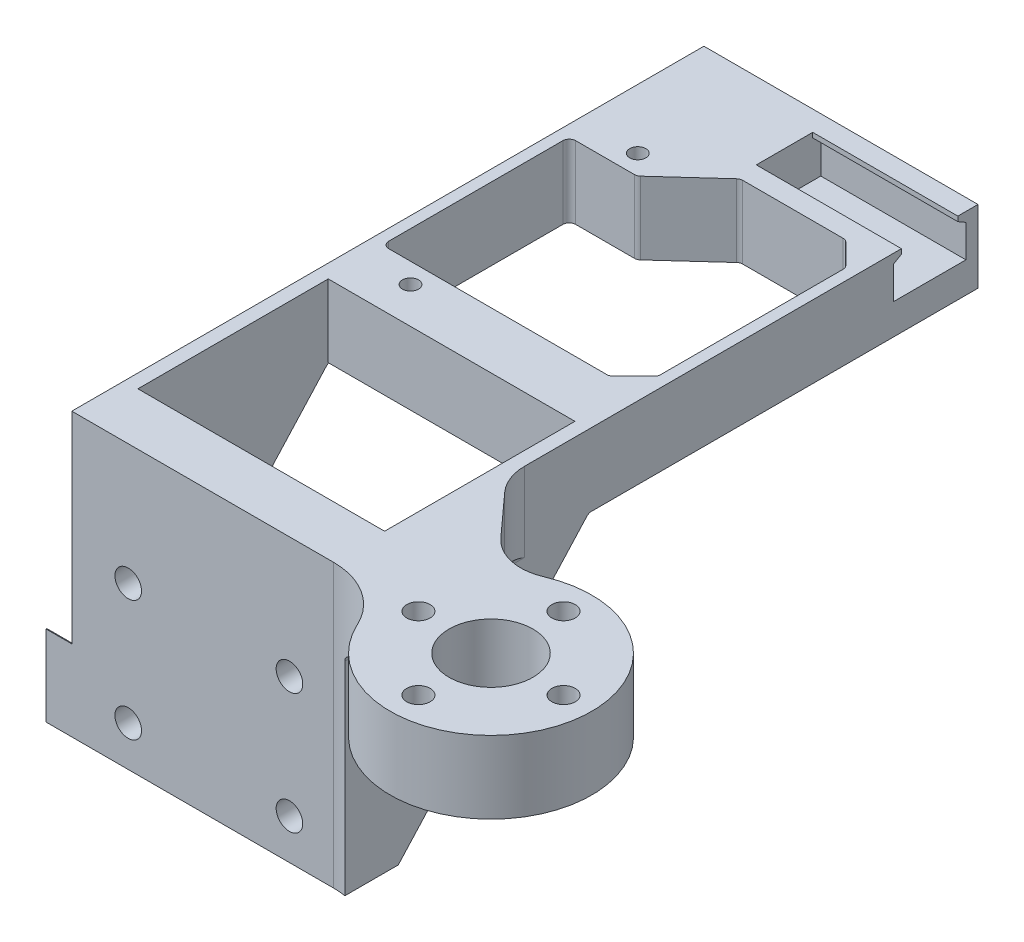
SolidWorks part; units mm, degrees
ref_plane "Front Plane" through (0, 0, 0) normal (0, 0, 1) x (1, 0, 0)
ref_plane "Top Plane" through (0, 0, 0) normal (0, 1, 0) x (1, 0, 0)
ref_plane "Right Plane" through (0, 0, 0) normal (1, 0, 0) x (0, 0, -1)
sketch "Sketch1" plane through (0, 0, 0) normal (0, 1, 0) x (1, 0, 0)
  line L0 (0, 0) -> (0, 59.6401) construction
  line L1 (-20, -19.2885) -> (-21.4, -19.2885)
  line L2 (20, 17.7115) -> (21.4, 17.7115)
  line L3 (20, 17.7115) -> (20, 69.9115)
  line L4 (20, 69.9115) -> (21.4, 69.9115)
  line L5 (21.4, 17.7115) -> (21.4, 69.9115)
  line L6 (20, 17.7115) -> (21.4, 17.7115)
  line L7 (20, 17.7115) -> (20, -19.2885)
  line L8 (20, -19.2885) -> (21.4, -19.2885)
  line L9 (21.4, 17.7115) -> (21.4, -19.2885)
  line L10 (-21.4, 17.7115) -> (-21.4, -19.2885)
  line L11 (-20, 17.7115) -> (-21.4, 17.7115)
  line L12 (-20, 17.7115) -> (-20, -19.2885)
  line L13 (-20, 69.9115) -> (-21.4, 69.9115)
  line L14 (-21.4, 17.7115) -> (-21.4, 69.9115)
  line L15 (-20, 17.7115) -> (-21.4, 17.7115)
  line L16 (-20, 17.7115) -> (-20, 69.9115)
  dimension "18" = 20
  dimension "D2" = 1.4
  dimension "D3" = 37
  dimension "D4" = 52.2
extrude "Boss-Extrude1" add sketch "Sketch1" against normal blind 9 from offset 1 contours L12 L11 L10 L1 | L11 L16 L13 L14 | L3 L2 L5 L4 offset against normal yes
sketch "Sketch4" plane through (0, -10, 0) normal (0, -1, 0) x (1, 0, 0)
  line L0 (-21.4, -69.9115) -> (-21.4, 19.2885) construction
  line L1 (12, -69.9115) -> (-21.4, -69.9115)
  line L2 (12, -69.9115) -> (12, -57.9115)
  line L3 (12, -57.9115) -> (-21.4, -57.9115)
  line L4 (-21.4, -69.9115) -> (-21.4, -57.9115)
  line L10 (-20, -69.9115) -> (-20, 19.2885) construction
  line L13 (-20, -69.9115) -> (-21.4, -69.9115) construction
  dimension "D1" = 12
  dimension "D2" = 32
extrude "Boss-Extrude3" add sketch "Sketch4" against normal up to surface (9 mm away) up to face at (-20.7, -1, -25.3115)
sketch "Sketch3" plane through (0, -10, 0) normal (0, -1, 0) x (1, 0, 0)
  line L0 (-21.4, -69.9115) -> (-21.4, 19.2885) construction
  line L1 (-21.4, -58.8115) -> (-7.4, -58.8115)
  line L2 (-21.4, -58.8115) -> (-21.4, -51.8115)
  line L3 (-21.4, -51.8115) -> (-7.4, -51.8115)
  line L4 (-7.4, -58.8115) -> (-7.4, -51.8115)
  line L6 (0, 0) -> (0, -31.4212) construction
  line L13 (12, -69.9115) -> (-21.4, -69.9115) construction
  line L14 (-21.4, -40.2115) -> (-3.8096, -40.2115) construction
  line L15 (-21.4, -28.6115) -> (-7.4, -28.6115)
  line L16 (-7.4, -21.6115) -> (-7.4, -28.6115)
  line L17 (-21.4, -21.6115) -> (-7.4, -21.6115)
  line L18 (-21.4, -21.6115) -> (-21.4, -28.6115)
  line L19 (-20, -57.9115) -> (-20, 19.2885) construction
  circle A0 centre (-14, -54.3115) radius 1
  circle A2 centre (-14, -26.1115) radius 1
  dimension "D4" = 2.5
  dimension "D5" = 2
  dimension "D1" = 14.1
  dimension "D2" = 15.6
  dimension "D3" = 7
  dimension "D6" = 6
  dimension "D7" = 14
extrude "Servo Holder" add sketch "Sketch3" along normal blind 1 and the other way offset from surface (9 mm away) 1 other way up to plane "Top Plane"
sketch "Sketch37" plane through (0, -1, 0) normal (0, 1, 0) x (1, 0, 0)
  line L0 (-7.4, 21.6115) -> (-20, 21.6115) construction
  line L1 (12.6, 21.6115) -> (-7.4, 21.6115)
  line L2 (12.6, 21.6115) -> (12.6, 28.6115)
  line L3 (12.6, 28.6115) -> (-7.4, 28.6115)
  line L4 (-7.4, 21.6115) -> (-7.4, 28.6115)
  line L5 (-21.4, 69.9115) -> (-21.4, -19.2885) construction
  dimension "D1" = 34
extrude "Boss-Extrude19" add sketch "Sketch37" against normal up to surface (10 mm away) up to face at (-14.4, -11, -25.1115)
sketch "Sketch29" plane through (0, 0, -69.9115) normal (0, 0, -1) x (-1, 0, 0)
  line L1 (21.4, -10) -> (-12.7099, -10)
  line L2 (21.4, -10) -> (21.4, -16.1774)
  line L3 (21.4, -16.1774) -> (-12.7099, -16.1774)
  line L4 (-12.7099, -10) -> (-12.7099, -16.1774)
extrude "Cut-Extrude10" cut sketch "Sketch29" against normal through all both and the other way through all
sketch "Sketch30" plane through (0, 0, 0) normal (0, 0, 1) x (1, 0, 0)
  line L0 (-4.4, -1) -> (-4.4, -36) construction
  line L1 (12.6, -1) -> (-21.4, -1)
  line L2 (12.6, -1) -> (12.6, -36)
  line L3 (12.6, -36) -> (-21.4, -36)
  line L4 (-21.4, -1) -> (-21.4, -36)
  line L7 (-21.4, -1) -> (12.6, -1) construction
  line L9 (12.6, -1) -> (-20, -1) construction
  line L11 (-21.4, -10) -> (-21.4, -1) construction
  circle A0 centre (5.6, -31) radius 1.65
  circle A1 centre (5.6, -16) radius 1.65
  circle A2 centre (-14.4, -31) radius 1.65
  circle A3 centre (-14.4, -16) radius 1.65
  dimension "D2" = 10
  dimension "D4" = 15
  dimension "D7" = 3.3
  dimension "D8" = 3.3
  dimension "D1" = 17
  dimension "D3" = 35
  dimension "D5" = 15
  dimension "D6" = 10
extrude "Carriage Interface" add sketch "Sketch30" along normal blind 6.5 from offset 2 separate body
sketch "Sketch41" plane through (-20, 0, 0) normal (1, 0, 0) x (0, 0, -1)
  line L0 (21.6115, -1) -> (-19.2885, -1) construction
  line L1 (-2, -1) -> (-19.2885, -1)
  line L2 (-2, -1) -> (-2, -10)
  line L3 (-2, -10) -> (-19.2885, -10)
  line L4 (-19.2885, -1) -> (-19.2885, -10)
  line L5 (-2, -1) -> (-2, -36) construction
extrude "Cut-Extrude14" cut sketch "Sketch41" against normal blind 15
sketch "Sketch32" plane through (0, -36, 0) normal (0, -1, 0) x (1, 0, 0)
  line L0 (-21.4, 8.5) -> (12.6, 8.5) construction
  line L1 (30.6, 8.5) -> (18.1, 8.5) construction
  line L2 (30.6, 8.5) -> (12.6, 8.5) construction
  line L4 (-21.4, 8.5) -> (12.6, 8.5) construction
  circle A0 centre (30.6, 8.5) radius 5.2
  circle A1 centre (30.6, 8.5) radius 12.5
  circle A2 centre (21.6, 8.5) radius 1.45
  circle A3 centre (30.6, 17.5) radius 1.45
  circle A4 centre (39.6, 8.5) radius 1.45
  circle A5 centre (30.6, -0.5) radius 1.45
  point P4 (-4.4, 8.5)
  point P18 (30.6, 8.5)
  line M1 (-21.4, 2) -> (12.6, 2)
  line M2 (12.6, 2) -> (12.6, 8.5)
  line M3 (12.6, 8.5) -> (-21.4, 8.5)
  dimension "D1" = 9
  dimension "D2" = 25
  dimension "D4" = 10.4
  dimension "D5" = 35
  dimension "D3" = 4
extrude "Trap Nut Interface" add sketch "Sketch32" along normal blind 9 from surface at -35 contours A1 A5 A4 A3 A2 A0 M1 M3 M2 starting at face at (-3.7, -1, 5.25)
sketch "Sketch34" plane through (-21.4, 0, 0) normal (-1, 0, 0) x (0, 0, 1)
  line L1 (-21.6115, -1) -> (-21.6115, -10)
  line L5 (-69.9115, -1) -> (2, -1) construction
  line L6 (-69.9115, -10) -> (2, -10) construction
  line L7 (-21.6115, -10) -> (2, -36)
  line L8 (-21.6115, -10) -> (-21.6115, -1) construction
  line L9 (2, -36) -> (8.5, -36)
  line L10 (8.5, -36) -> (8.5, -1)
  line L11 (8.5, -1) -> (-21.6115, -1)
extrude "Boss-Extrude16" add sketch "Sketch34" against normal blind 1.7
sketch "Sketch35" plane through (12.6, 0, 0) normal (1, 0, 0) x (0, 0, -1)
  line L0 (-2, -1) -> (21.6115, -1)
  line L1 (21.6115, -1) -> (21.6115, -10)
  line L3 (-8.5, -9.8) -> (-8.5, -1)
  line L4 (-8.5, -1) -> (-2, -1)
  line L5 (21.6115, -10) -> (21.6115, -1) construction
  line L6 (28.6115, -10) -> (21.6115, -10) construction
  line L8 (-8.5, -36) -> (-8.5, -1) construction
  line L9 (21.6115, -1) -> (28.6115, -1) construction
  line L10 (21.6115, -10) -> (-2, -36)
  line L11 (-2, -36) -> (-8.5, -36)
  line L12 (-8.5, -36) -> (-8.5, -9.8)
extrude "Boss-Extrude17" add sketch "Sketch35" against normal blind 1.7
sketch "Sketch36" plane through (0, -10, 0) normal (0, -1, 0) x (1, 0, 0)
  line L0 (12.6, -11.3656) -> (22.2068, -0.7631)
  line L1 (12.6, 8.5) -> (19.7685, 8.5)
  line L2 (22.2068, -0.7631) -> (12.6, -0.1224)
  line L3 (12.6, -0.1224) -> (12.6, -11.3656)
  line L4 (30.6, 8.5) -> (12.6, -11.3656) construction
  line L5 (12.6, 8.5) -> (12.6, 2) construction
  line L6 (19.7685, 8.5) -> (22.2068, -0.7631)
  line L7 (12.6, 8.5) -> (12.6, -0.1224)
  circle A1 centre (30.6, 8.5) radius 12.5 construction
  point P8 (20.15, 8.5)
  point P13 (19.7685, 8.5)
  point P15 (20.15, 8.5)
extrude "Boss-Extrude18" add sketch "Sketch36" against normal up to surface (9 mm away) contours L1 L7 L2 L6 | L2 L3 L0
fillet "Fillet9" [suppressed] radius 1
sketch "Sketch39" plane through (0, -1, 0) normal (0, 1, 0) x (1, 0, 0)
  line L0 (-21.4, 69.9115) -> (12, 69.9115) construction
  line L1 (12.6, 28.6115) -> (11.2, 28.6115)
  line L2 (12.6, 28.6115) -> (12.6, 69.9115)
  line L3 (12.6, 69.9115) -> (11.2, 69.9115)
  line L4 (11.2, 28.6115) -> (11.2, 69.9115)
  line L5 (-20, 28.6115) -> (12.6, 28.6115) construction
  line L6 (12.6, 11.3656) -> (12.6, 28.6115) construction
  point P7 (12.6, 49.2615)
  dimension "D1" = 1.4
extrude "Boss-Extrude20" add sketch "Sketch39" against normal up to surface (9 mm away) up to face at (-4.7667, -10, -41.9115)
sketch "Sketch40" plane through (12.6, 0, 0) normal (1, 0, 0) x (0, 0, -1)
  line L1 (60.4115, -1) -> (67.4115, -1)
  line L6 (60.4115, -2.2) -> (59.4115, -2.2)
  line L7 (59.4115, -2.2) -> (59.4115, -6.2)
  line L8 (59.4115, -6.2) -> (68.4115, -6.2)
  line L9 (63.9115, -6.2) -> (63.9115, -1)
  line L11 (68.4115, -2.2) -> (68.4115, -6.2)
  line L12 (67.4115, -2.2) -> (68.4115, -2.2)
  line L13 (67.4115, -1) -> (67.4115, -2.2)
  line L14 (69.9115, -10) -> (69.9115, -1) construction
  line L15 (60.4115, -2.2) -> (60.4115, -1)
  line L16 (11.3656, -1) -> (69.9115, -1) construction
  point P9 (59.4115, -4.2)
  dimension "D1" = 6
  dimension "D2" = 3.5
  dimension "D3" = 4.5
  dimension "D4" = 4
  dimension "D5" = 1.2
  dimension "D6" = 3.5
  dimension "D7" = 1
extrude "Brush" cut sketch "Sketch40" against normal blind 18
chamfer "Chamfer2" distance 0.6 angle 60 2 edges at (3.6, -2.2, -67.4115) (3.6, -2.2, -60.4115)
chamfer "Chamfer3" distance 3 angle 45 2 edges at (11.2, -5.5, -28.6115) (11.2, -5.5, -57.9115)
fillet "Fillet10" radius 6 2 edges at (22.2068, -5.5, -0.7631) (12.6, -5.5, -11.3656)
sketch "Sketch42" plane through (0, 0, 8.5) normal (0, 0, 1) x (1, 0, 0)
  line L0 (-4.4, -36) -> (-4.4, -1) construction
  line L3 (-21.4, -36) -> (12.6, -36) construction
  line L4 (18.1, -1) -> (-21.4, -1) construction
  line L5 (-0.8, -1) -> (-0.8, -10.6)
  line L6 (-8, -1) -> (-8, -10.6)
  line L7 (-0.8, -1) -> (-8, -1)
  arc A0 (-0.8, -10.6) -> (-8, -10.6) centre (-4.4, -10.6) cw
  point P11 (-4.4, -14.2)
  dimension "D1" = 3.6
  dimension "D2" = 13.2
extrude "Cut-Extrude15" [suppressed] cut sketch "Sketch42" against normal blind 10
chamfer "Chamfer4" distance 2.5 angle 45 1 edges at (-7.4, -5.5, -57.9115)
sketch "Sketch43" plane through (0, -1, 0) normal (0, 1, 0) x (1, 0, 0)
  line L0 (-4.9, 57.9115) -> (-11.6, 51.8115)
  line L1 (-7.4, 51.8115) -> (-20, 51.8115) construction
  line L2 (-11.6, 51.8115) -> (-4.9, 51.8115)
  line L3 (-4.9, 51.8115) -> (-4.9, 57.9115)
extrude "Cut-Extrude16" cut sketch "Sketch43" against normal blind 10
fillet "Fillet11" radius 0.8 10 edges at (11.2, -5.5, -54.9115) (11.2, -5.5, -31.6115) (8.2, -5.5, -28.6115) (8.2, -5.5, -57.9115) (-4.9, -5.5, -57.9115) (-11.6, -5.5, -51.8115) (-20, -5.5, -28.6115) (-20, -5.5, -51.8115) (-20.55, -10, -21.6115) (11.75, -10, -21.6115)
fillet "Fillet12" radius 9 1 edges at (18.1, -5.5, 8.5)
sketch "Sketch44" plane through (0, -36, 0) normal (0, -1, 0) x (1, 0, 0)
  line L0 (-21.4, 8.5) -> (-24.6, 8.5)
  line L1 (-24.6, 8.5) -> (-24.6, 1.4)
  line L2 (-24.6, 1.4) -> (-22.9, 1.4)
  line L3 (-22.9, 1.4) -> (-22.9, 6.8)
  line L4 (-22.9, 6.8) -> (-21.4, 6.8)
  line L5 (-21.4, 2) -> (-21.4, 8.5) construction
  line L6 (-22.9, 1.4) -> (-22.2, 1.9334)
  line L7 (-22.2, 1.9334) -> (-22.9, 2.4)
  line L8 (-22.9, 2.4) -> (-22.9, 1.4)
  line M13 (-21.4, 8.5) -> (-21.4, 2)
  dimension "D1" = 1.7
  dimension "D2" = 1.7
  dimension "D3" = 5.4
  dimension "D4" = 1.5
  dimension "D5" = 4.4
  dimension "D6" = 0.7
extrude "Boss-Extrude21" add sketch "Sketch44" against normal blind 10 contours L3 L4 L0 L1 L2 M13 | L6 L7 L3
chamfer "Chamfer5" distance 7 angle 45 1 edges at (-23.75, -26, 1.4)
chamfer "Chamfer6" distance 1.5 angle 30 1 edges at (-22.15, -36, 6.8)
fillet "Fillet13" radius 1 1 edges at (-22.15, -34.5, 6.8)
